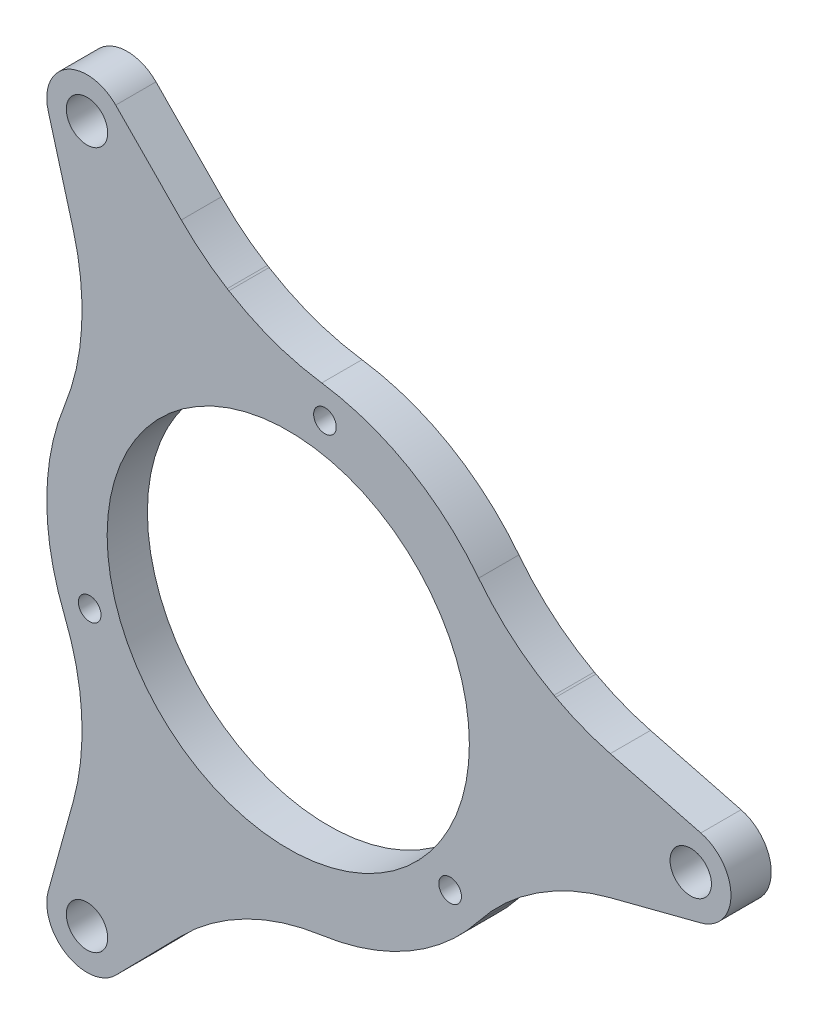
SolidWorks part; units mm, degrees
ref_plane "Front Plane" through (0, 0, 0) normal (0, 0, 1) x (1, 0, 0)
ref_plane "Top Plane" through (0, 0, 0) normal (0, 1, 0) x (1, 0, 0)
ref_plane "Right Plane" through (0, 0, 0) normal (1, 0, 0) x (0, 0, -1)
sketch "Sketch1" plane through (0, 0, 0) normal (0, 0, 1) x (1, 0, 0)
  line L0 (0, 0) -> (0, 31.75) construction
  line L1 (27.4963, 15.875) -> (38.4948, 22.225)
  line L2 (27.4963, -15.875) -> (38.4948, -22.225)
  line L3 (0, -31.75) -> (0, -44.45)
  line L4 (-27.4963, -15.875) -> (-38.4948, -22.225)
  line L5 (-27.4963, 15.875) -> (-38.4948, 22.225)
  line L6 (0, 31.75) -> (0, 44.45)
  line L7 (-20.9623, -0.7492) -> (-20.9623, -0.7492)
  line L8 (-9.8323, -18.5285) -> (-9.8323, -18.5285)
  line L9 (11.13, -17.7793) -> (11.13, -17.7793)
  line L10 (20.9623, 0.7492) -> (20.9623, 0.7492)
  line L11 (9.8323, 18.5285) -> (9.8323, 18.5285)
  line L12 (-11.13, 17.7793) -> (-11.13, 17.7793)
  line L13 (27.4963, 15.875) -> (24.4114, 20.9701) construction
  arc A0 (-11.13, 17.7793) -> (-20.9623, -0.7492) centre (39.2347, -20.8203) ccw
  arc A1 (38.4948, -22.225) -> (27.4963, 15.875) centre (-37.6483, -23.5681) ccw
  arc A2 (38.4948, 22.225) -> (0, 31.75) centre (1.5864, -44.3884) ccw
  arc A3 (0, -44.45) -> (27.4963, -15.875) centre (-39.2347, 20.8203) ccw
  arc A4 (-38.4948, -22.225) -> (0, -31.75) centre (-1.5864, 44.3884) ccw
  arc A5 (-38.4948, 22.225) -> (-27.4963, -15.875) centre (37.6483, 23.5681) ccw
  arc A6 (0, 44.45) -> (-27.4963, 15.875) centre (39.2347, -20.8203) ccw
  arc A7 (-20.9623, -0.7492) -> (-9.8323, -18.5285) centre (37.6483, 23.5681) ccw
  arc A8 (-9.8323, -18.5285) -> (11.13, -17.7793) centre (-1.5864, 44.3884) ccw
  arc A9 (11.13, -17.7793) -> (20.9623, 0.7492) centre (-39.2347, 20.8203) ccw
  arc A10 (20.9623, 0.7492) -> (9.8323, 18.5285) centre (-37.6483, -23.5681) ccw
  arc A11 (9.8323, 18.5285) -> (-11.13, 17.7793) centre (1.5864, -44.3884) ccw
  point P3 (0, 0)
  point P7 (42.5077, 12.9959)
  point P32 (0, 0)
  dimension "D1" = 6
  dimension "D2" = 12.7
  dimension "D3" = 60
extrude "Boss-Extrude1" add sketch "Sketch1" along normal blind 6.35 and the other way blind 6.35
sketch "Sketch3" plane through (0, 0, 6.35) normal (0, 0, 1) x (1, 0, 0)
  arc A0 (-11.13, 17.7793) -> (-20.9623, -0.7492) centre (39.2347, -20.8203) ccw construction
  arc A1 (9.8323, 18.5285) -> (-11.13, 17.7793) centre (1.5864, -44.3884) ccw construction
  arc A2 (20.9623, 0.7492) -> (9.8323, 18.5285) centre (-37.6483, -23.5681) ccw construction
  arc A3 (11.13, -17.7793) -> (20.9623, 0.7492) centre (-39.2347, 20.8203) ccw construction
  arc A4 (-9.8323, -18.5285) -> (11.13, -17.7793) centre (-1.5864, 44.3884) ccw construction
  arc A5 (-20.9623, -0.7492) -> (-9.8323, -18.5285) centre (37.6483, 23.5681) ccw construction
  arc A6 (-11.13, 17.7793) -> (-20.9623, -0.7492) centre (39.2347, -20.8203) ccw
  arc A7 (9.8323, 18.5285) -> (-11.13, 17.7793) centre (1.5864, -44.3884) ccw
  arc A8 (20.9623, 0.7492) -> (9.8323, 18.5285) centre (-37.6483, -23.5681) ccw
  arc A9 (11.13, -17.7793) -> (20.9623, 0.7492) centre (-39.2347, 20.8203) ccw
  arc A10 (-9.8323, -18.5285) -> (11.13, -17.7793) centre (-1.5864, 44.3884) ccw
  arc A11 (-20.9623, -0.7492) -> (-9.8323, -18.5285) centre (37.6483, 23.5681) ccw
extrude "Boss-Extrude2" add sketch "Sketch3" against normal blind 12.7
sketch "Sketch4" plane through (0, 0, 6.35) normal (0, 0, 1) x (1, 0, 0)
  circle A0 centre (0, 0) radius 28.575
  dimension "D1" = 57.15
extrude "Cut-Extrude1" cut sketch "Sketch4" against normal through all
sketch "Sketch5" plane through (0, 0, -6.35) normal (0, 0, -1) x (-1, 0, 0)
  line L0 (0, 0) -> (-63.5, 0) construction
  line L1 (-46.2935, -11.0113) -> (-58.2176, -7.926)
  line L2 (-46.2935, 11.0113) -> (-65.0907, 6.1477)
  line L3 (13.6107, 45.597) -> (27.2213, 59.444)
  line L4 (32.6828, 34.5857) -> (37.8694, 53.2963)
  line L5 (32.6828, -34.5857) -> (37.8694, -53.2963)
  line L6 (13.6107, -45.597) -> (27.2213, -59.444)
  line L10 (-58.2176, -7.926) -> (-65.0907, -6.1477)
  line L13 (-33.6539, -17.8612) -> (-46.2935, -11.0113)
  line L14 (1.3587, -38.0758) -> (13.6107, -45.597)
  line L15 (1.3587, 38.0758) -> (13.6107, 45.597)
  line L16 (-33.6539, 17.8612) -> (-46.2935, 11.0113)
  line L17 (32.2952, -20.2146) -> (32.6828, -34.5857)
  line L18 (32.2952, 20.2146) -> (32.6828, 34.5857)
  arc A0 (-65.0907, 6.1477) -> (-65.0907, -6.1477) centre (-63.5, 0) ccw
  arc A1 (37.8694, 53.2963) -> (27.2213, 59.444) centre (31.75, 54.9926) ccw
  arc A2 (27.2213, -59.444) -> (37.8694, -53.2963) centre (31.75, -54.9926) ccw
  circle A3 centre (0, 0) radius 28.575
  arc A4 (1.3587, 38.0758) -> (-33.6539, 17.8612) centre (0, 0) ccw
  arc A5 (-33.6539, -17.8612) -> (1.3587, -38.0758) centre (0, 0) ccw
  arc A6 (32.2952, -20.2146) -> (32.2952, 20.2146) centre (0, 0) ccw
  circle A7 centre (31.75, 54.9926) radius 3.175 construction
  circle A8 centre (31.75, -54.9926) radius 3.175 construction
  circle A9 centre (-63.5, 0) radius 3.175 construction
  point P21 (0, 0)
  point P22 (31.75, 54.9926)
  point P26 (53.975, 54.9926)
  point P27 (0, 0)
  point P33 (0, 0)
  point P34 (0, 0)
  point P36 (41.275, 0)
  point P52 (0, 0)
  point P60 (0, 0)
  dimension "D2" = 12.7002
  dimension "D4" = 3
  dimension "D1" = 63.5
  dimension "D3" = 3
  dimension "D8" = 3
extrude "Boss-Extrude3" add sketch "Sketch5" along normal blind 6.35
hole_wizard "F (0.257) Diameter Hole1" positions "Sketch7" profile "Sketch6" hole size "F" standard "ANSI Inch" end condition through all
sketch "Sketch7" plane through (0, 0, -6.35) normal (0, 0, 1) x (1, 0, 0)
  point P0 (-31.75, 54.9926)
  point P7 (63.5, 0)
  point P8 (-31.75, -54.9926)
  point P9 (0, 0)
  dimension "D1" = 3
sketch "Sketch6" plane through (-31.75, 54.9926, -6.35) normal (1, 0, 0) x (0, -1, 0)
  line L0 (0, 0) -> (0, 6.35)
  line L1 (0, 6.35) -> (3.2639, 6.35)
  line L2 (3.2639, 6.35) -> (3.2639, 0)
  line L5 (3.2639, 0) -> (0, 0)
  line L11 (0, -6.35) -> (0, 107.95) construction
  dimension "Thru Hole Dia." = 6.5278
  dimension "Thru Hole Depth" = 6.35
sketch "Sketch8" plane through (0, 0, 0) normal (1, 0, 0) x (0, 0, -1)
  line L1 (-6.35, 44.45) -> (6.35, 44.45)
  line L2 (-6.35, 44.45) -> (-6.35, -44.45)
  line L3 (-6.35, -44.45) -> (6.35, -44.45)
  line L4 (6.35, 44.45) -> (6.35, -44.45)
extrude "Cut-Extrude2" cut sketch "Sketch8" against normal through all both and the other way through all
fillet "Fillet3" radius 38.1 12 edges at (-13.6107, -45.597, -9.525) (-1.3587, -38.0758, -9.525) (33.6539, -17.8612, -9.525) (46.2935, -11.0113, -9.525) (46.2935, 11.0113, -9.525) (33.6539, 17.8612, -9.525) (-1.3587, 38.0758, -9.525) (-13.6107, 45.597, -9.525) (-32.6828, 34.5857, -9.525) (-32.2952, 20.2146, -9.525) (-32.2952, -20.2146, -9.525) (-32.6828, -34.5857, -9.525)
sketch "Sketch10" plane through (0, 0, -12.7) normal (0, 0, -1) x (-1, 0, 0)
  circle A0 centre (-5.789, 32.831) radius 1.786
  circle A1 centre (31.327, -11.4021) radius 1.786
  circle A2 centre (-25.538, -21.4289) radius 1.786
  point P9 (0, 0)
  dimension "D1" = 3
extrude "Cut-Extrude4" cut sketch "Sketch10" against normal through all
